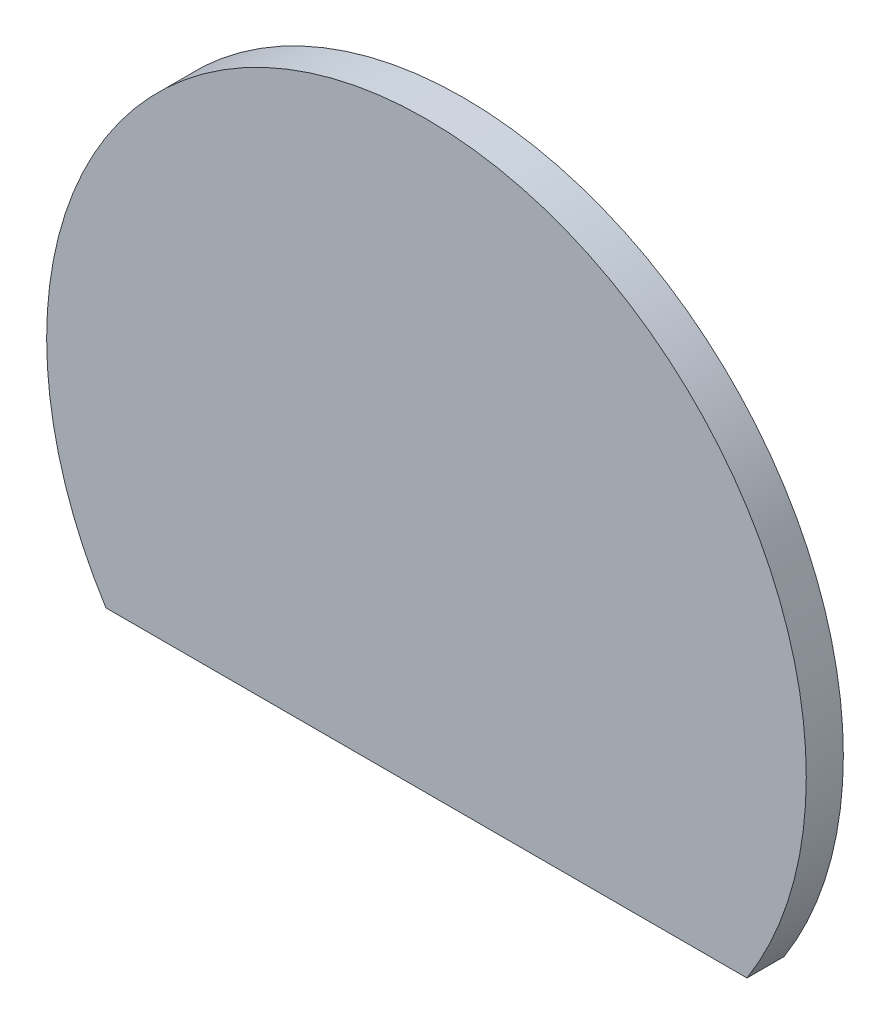
SolidWorks part; units mm, degrees
ref_plane "Front Plane" through (0, 0, 0) normal (0, 0, 1) x (1, 0, 0)
ref_plane "Top Plane" through (0, 0, 0) normal (0, 1, 0) x (1, 0, 0)
ref_plane "Right Plane" through (0, 0, 0) normal (1, 0, 0) x (0, 0, -1)
sketch "Sketch1" plane through (0, 0, 0) normal (0, 0, 1) x (1, 0, 0)
  line L0 (-8.6494, -5.5) -> (8.6494, -5.5)
  arc A0 (8.6494, -5.5) -> (-8.6494, -5.5) centre (0, 0) ccw
  circle A1 centre (0, 0) radius 4.5
  circle A2 centre (0, 0) radius 5.5
  dimension "D1" = 20.5
  dimension "D2" = 9
  dimension "D3" = 1
extrude "Boss-Extrude1" add sketch "Sketch1" along normal blind 1 contours L0 A2 A0 | A1 | A2 A1 region at (-3.7791, 3.7791, 0) region at (0, 9.9915, 0) region at (0, 0, 0)
sketch "Sketch3" plane through (0, 0, 0) normal (0, 0, -1) x (-1, 0, 0)
  circle A0 centre (0, 0) radius 3.5
  circle A1 centre (0, 0) radius 4.5
extrude "Boss-Extrude2" add sketch "Sketch3" along normal blind 2.2
